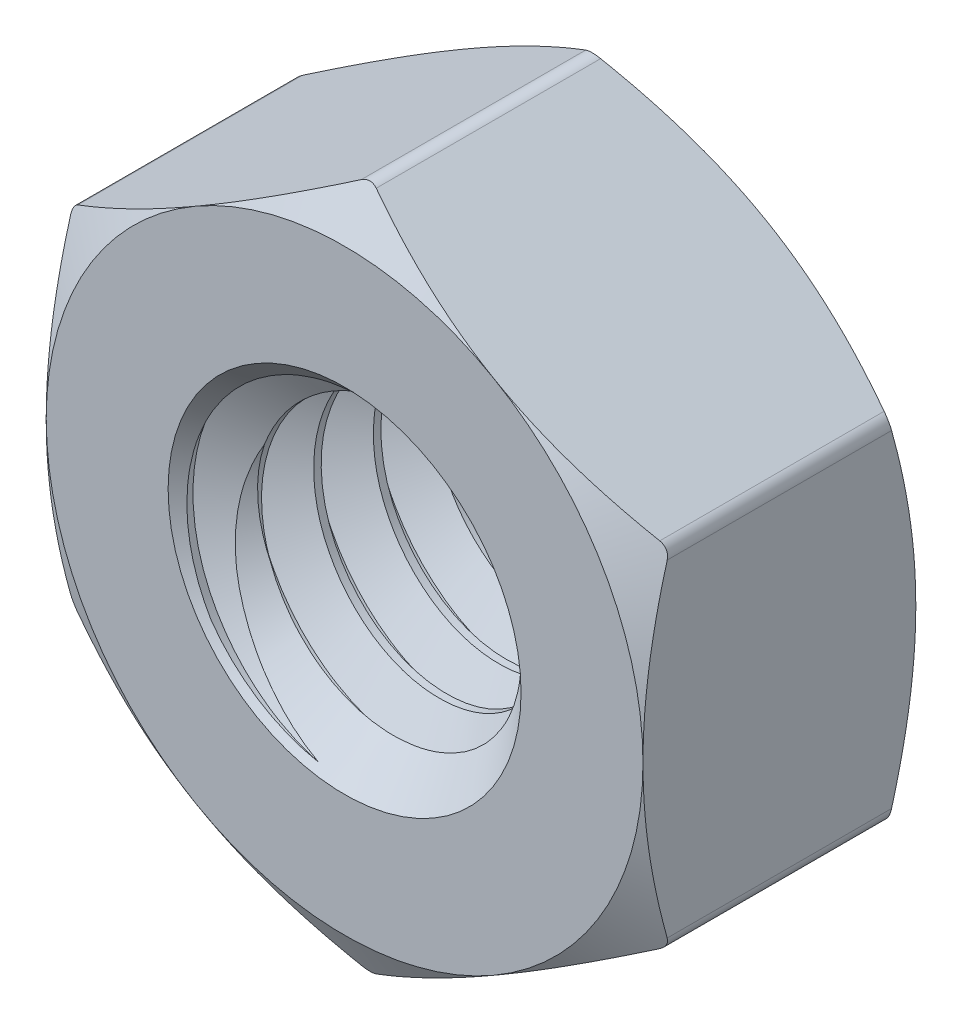
SolidWorks part; units mm, degrees
ref_plane "Front" through (0, 0, 0) normal (0, 0, 1) x (1, 0, 0)
ref_plane "Top" through (0, 0, 0) normal (0, 1, 0) x (1, 0, 0)
ref_plane "Right" through (0, 0, 0) normal (1, 0, 0) x (0, 0, -1)
sketch "Sketch1" plane through (0, 0, 0) normal (0, 0, 1) x (1, 0, 0)
  line L0 (0, 2) -> (0, 1.3) construction
  line L1 (-3.5, 2.0207) -> (-3.5, -2.0207)
  line L2 (-3.5, -2.0207) -> (0, -4.0415)
  line L3 (0, -4.0415) -> (3.5, -2.0207)
  line L4 (3.5, -2.0207) -> (3.5, 2.0207)
  line L5 (3.5, 2.0207) -> (0, 4.0415)
  line L6 (0, 4.0415) -> (-3.5, 2.0207)
  circle A0 centre (0, 0) radius 3.5 construction
  circle A1 centre (0, 0) radius 2 construction
  point P10 (0, 2)
  dimension "Width" = 7
  dimension "Thread Size" = 4
  dimension "Thread Pitch" = 0.7
sketch "Sketch2" plane through (0, 0, 0) normal (1, 0, 0) x (0, 0, -1)
  line L0 (-1.6, 0) -> (1.6, 0) construction
  line L1 (-1.6, 4.0415) -> (1.6, 4.0415) construction
  dimension "Height" = 3.2
sketch "Sketch15" plane through (0, 0, 0) normal (0, 0, 1) x (1, 0, 0)
  line L1 (0, 4.0415) -> (-3.5, 2.0207)
  line L2 (-3.5, 2.0207) -> (-3.5, -2.0207)
  line L3 (-3.5, -2.0207) -> (0, -4.0415)
  line L4 (0, -4.0415) -> (3.5, -2.0207)
  line L5 (3.5, -2.0207) -> (3.5, 2.0207)
  line L6 (3.5, 2.0207) -> (0, 4.0415)
  circle A0 centre (0, 0) radius 3.5 construction
extrude "Boss-Extrude2" add sketch "Sketch15" along normal mid plane 3.2
sketch "Sketch16" plane through (0, 0, 0) normal (0, 0, 1) x (1, 0, 0)
  circle A0 centre (0, 0) radius 2 construction
  circle A1 centre (0, 0) radius 2
sketch "Sketch4" plane through (0, 0, -1.6) normal (0, 0, -1) x (-1, 0, 0)
  circle A0 centre (0, 0) radius 2 construction
  circle A1 centre (0, 0) radius 2
extrude "Cut-Extrude4" cut sketch "Sketch16" against normal through all both and the other way through all
sketch "Sketch7" plane through (0, 0, 1.6) normal (0, 0, 1) x (1, 0, 0)
  circle A0 centre (0, 0) radius 3.5 construction
  circle A1 centre (0, 0) radius 3.5
extrude "Cut-Extrude5" cut sketch "Sketch7" against normal through all draft 60 flip side to cut
mirror "Mirror4" about plane through (0, 0, 0) normal (0, 0, 1) of "Cut-Extrude5"
fillet "Fillet2" radius 0.175 6 edges at (-3.5, 2.0207, 0) (-3.5, -2.0207, 0) (0, -4.0415, 0) (3.5, -2.0207, 0) (3.5, 2.0207, 0) (0, 4.0415, 0)
sketch "Sketch8" plane through (0, 0, 1.6) normal (0, 0, 1) x (1, 0, 0)
  line L0 (0.5176, -1.9319) -> (0, 0) construction
  line L2 (0, 2) -> (0, 1.3) construction
  circle A0 centre (0, 0) radius 2 construction
  point P0 (0.5176, -1.9319)
  dimension "D1" = 15
sketch "Sketch13" plane through (0, 0, -1.6) normal (0, 0, -1) x (-1, 0, 0)
  circle A0 centre (0, 0) radius 2 construction
  circle A1 centre (0, 0) radius 2
extrude "Boss-Extrude1" add sketch "Sketch13" against normal up to surface (3.2 mm away) separate body up to face at (2, 0, 1.6)
curve "Helix/Spiral3" pitch 0.7 height 3.2 radius 2 centre (0, 0, -1.6) axis (0, 0, 1) start towards (0, 1, 0)
sketch "Sketch12" plane through (0, 0, 0) normal (1, 0, 0) x (0, 0, -1)
  line L0 (2.2125, 2) -> (1.6, 2)
  line L1 (2.2125, 2) -> (1.95, 1.5453)
  line L2 (1.95, 1.5453) -> (1.8625, 1.5453)
  line L3 (1.8625, 1.5453) -> (1.6, 2)
  line L4 (1.9062, 1.5453) -> (1.9062, 2) construction
  line L5 (1.7313, 1.7727) -> (2.0812, 1.7727) construction
  dimension "D1" = 60
  dimension "D2" = 0.0875
  dimension "D3" = 0.35
sweep "Cut-Sweep1" cut profiles "Sketch12" path "Helix/Spiral3" align with end faces yes
sketch "Sketch17" plane through (0, 0, 1.6) normal (0, 0, 1) x (1, 0, 0)
  circle A1 centre (0, 0) radius 2
  circle A2 centre (0, 0) radius 2
  dimension "D1" = 0
extrude "Boss-Extrude3" add sketch "Sketch17" against normal up to surface (3.2 mm away) up to face at (2, 0, -1.6)
combine bodies "Combine1" operation type subtract main body 127 bodies to subtract 118
sketch "Sketch10" plane through (0, 0, 1.6) normal (0, 0, 1) x (1, 0, 0)
  circle A0 centre (0, 0) radius 2 construction
  circle A1 centre (0, 0) radius 2 construction
  circle A2 centre (0, 0) radius 2.07
  dimension "D1" = 0.07
extrude "Cut-Extrude2" cut sketch "Sketch10" against normal through all draft 45
sketch "Sketch11" plane through (0, 0, -1.6) normal (0, 0, -1) x (-1, 0, 0)
  circle A1 centre (0, 0) radius 2.07 construction
  circle A2 centre (0, 0) radius 2.07
extrude "Cut-Extrude3" cut sketch "Sketch11" against normal through all draft 45
equation "\"D1\"= \"Height@Sketch2\""
equation "\"D3@Helix/Spiral3\"=\"Height@Sketch2\""
equation "\"D4@Helix/Spiral3\"=\"Thread Pitch@Sketch1\""
equation "\"D2@Sketch12\" = \"D4@Helix/Spiral3\"*.125"
equation "\"D3@Sketch12\" = \"D4@Helix/Spiral3\"*.50"
equation "\"D1@Boss-Extrude2\"=\"Height@Sketch2\""
equation "\"D1@Fillet2\"=\"Width@Sketch1\"*0.025"
equation "\"D1@Sketch10\"=\"Thread Pitch@Sketch1\"*0.1"
